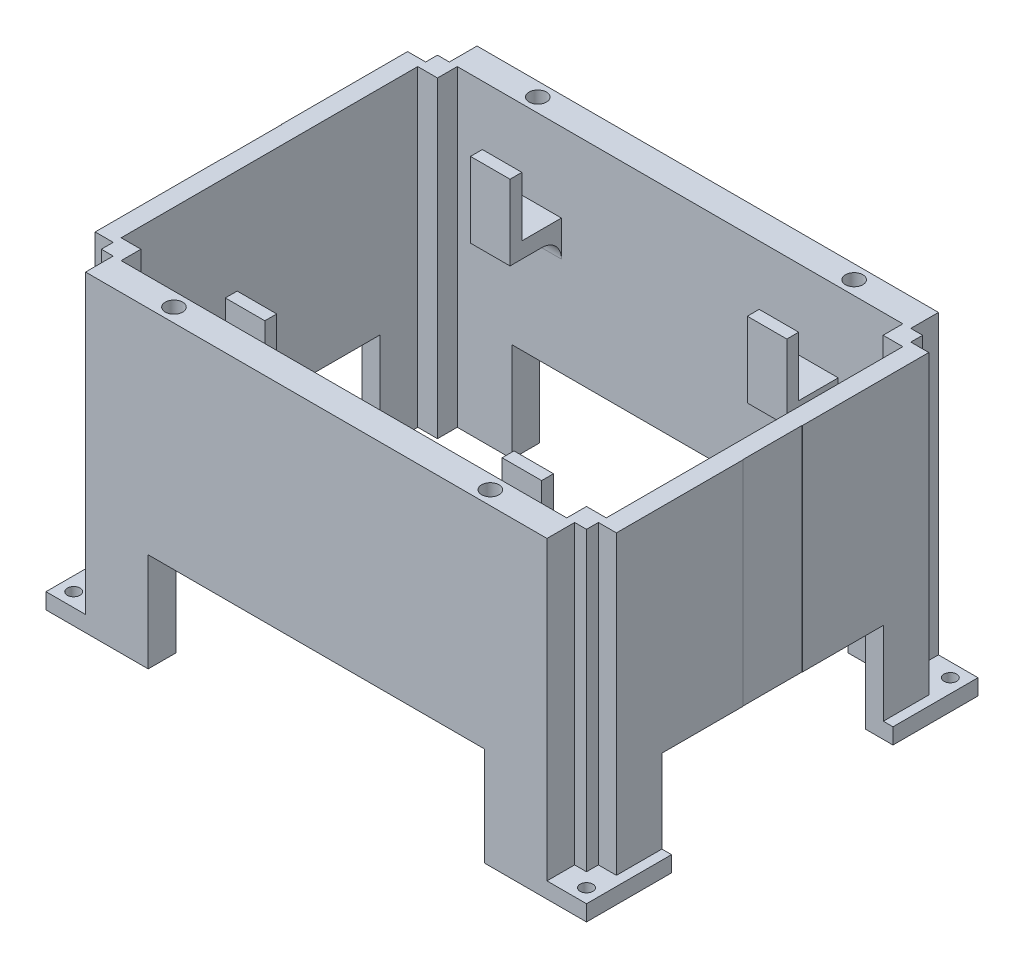
SolidWorks part; units mm, degrees
ref_plane "Front Plane" through (0, 0, 0) normal (0, 0, 1) x (1, 0, 0)
ref_plane "Top Plane" through (0, 0, 0) normal (0, 1, 0) x (1, 0, 0)
ref_plane "Right Plane" through (0, 0, 0) normal (1, 0, 0) x (0, 0, -1)
sketch "Sketch1" plane through (0, 0, 0) normal (0, 1, 0) x (1, 0, 0)
  line L0 (-68.342, -49.5) -> (-68.342, 49.5)
  line L1 (-61.342, -42.5) -> (61.342, -42.5)
  line L2 (-61.342, -42.5) -> (-61.342, 42.5)
  line L3 (-61.342, 42.5) -> (61.342, 42.5)
  line L4 (61.342, -42.5) -> (61.342, 42.5)
  line L5 (-61.342, -42.5) -> (61.342, 42.5) construction
  line L6 (-61.342, 42.5) -> (61.342, -42.5) construction
  line L7 (-68.342, 49.5) -> (68.342, 49.5)
  line L8 (68.342, -49.5) -> (68.342, 49.5)
  line L9 (-68.342, -49.5) -> (68.342, -49.5)
  line L10 (-68.342, 0) -> (-65.842, 0) construction
  line L11 (-65.842, 0) -> (-65.842, 7.5) construction
  line L12 (0, 0) -> (0, 42.5) construction
  line L13 (-70.842, -7.5) -> (-65.842, -7.5)
  line L14 (-70.842, -7.5) -> (-70.842, 7.5)
  line L15 (-70.842, 7.5) -> (-65.842, 7.5)
  line L16 (-65.842, -7.5) -> (-65.842, 7.5)
  line L17 (-70.842, -7.5) -> (-65.842, 7.5) construction
  line L18 (-70.842, 7.5) -> (-65.842, -7.5) construction
  line L19 (-72.842, -9.5) -> (-72.842, 9.5)
  line L20 (-72.842, 9.5) -> (-63.842, 9.5)
  line L21 (-63.842, -9.5) -> (-63.842, 9.5)
  line L22 (-72.842, -9.5) -> (-63.842, -9.5)
  line L23 (72.842, -9.5) -> (63.842, -9.5)
  line L24 (63.842, -9.5) -> (63.842, 9.5)
  line L25 (72.842, 9.5) -> (63.842, 9.5)
  line L26 (72.842, -9.5) -> (72.842, 9.5)
  line L27 (70.842, 7.5) -> (65.842, 7.5)
  line L28 (65.842, -7.5) -> (65.842, 7.5)
  line L29 (70.842, -7.5) -> (65.842, -7.5)
  line L30 (70.842, -7.5) -> (70.842, 7.5)
  line L31 (61.342, -37.5) -> (56.342, -37.5)
  line L32 (-61.342, -42.5) -> (-56.342, -42.5)
  line L33 (-61.342, -42.5) -> (-61.342, -37.5)
  line L34 (-61.342, -37.5) -> (-56.342, -37.5)
  line L35 (-56.342, -42.5) -> (-56.342, -37.5)
  line L36 (-61.342, 42.5) -> (-56.342, 42.5)
  line L37 (-61.342, 42.5) -> (-61.342, 37.5)
  line L38 (-61.342, 37.5) -> (-56.342, 37.5)
  line L39 (-56.342, 42.5) -> (-56.342, 37.5)
  line L40 (56.342, -42.5) -> (56.342, -37.5)
  line L41 (61.342, -42.5) -> (56.342, -42.5)
  line L42 (61.342, -42.5) -> (61.342, -37.5)
  line L43 (61.342, 37.5) -> (56.342, 37.5)
  line L44 (56.342, 42.5) -> (56.342, 37.5)
  line L45 (61.342, 42.5) -> (56.342, 42.5)
  line L46 (61.342, 42.5) -> (61.342, 37.5)
  point P0 (0, 0)
  dimension "D2" = 2
  dimension "D1" = 7
extrude "Boss-Extrude1" add sketch "Sketch1" along normal blind 4 contours L25 L8 L7 L0 L20 L21 L22 L9 L23 L24 L4 L1 L2 L3 | L0 L22 L21 L20 L15 L16 L13 | L8 L29 L28 L27 L25 L24 L23 region at (-66.6543, 0, 29.5) region at (-65.3108, 0, 0) region at (65.3108, 0, 0)
sketch "Sketch3" plane through (0, 0, 0) normal (0, 1, 0) x (1, 0, 0)
  line L0 (0, 0) -> (13.5974, 0) construction
  line L1 (0, 0) -> (0, -8.9797) construction
  line L2 (64.8156, -49.5) -> (64.8156, -46) construction
  line L3 (-68.342, -49.5) -> (68.342, -49.5) construction
  line L4 (68.342, -46) -> (64.842, -46) construction
  line L5 (68.342, -49.5) -> (68.342, -7.5) construction
  line L6 (0, 0) -> (0, 37.5) construction
  line L7 (0, 37.5) -> (-37.5, 37.5) construction
  circle A0 centre (64.842, -46) radius 1.6
  circle A1 centre (64.842, 46) radius 1.6
  circle A2 centre (-64.842, 46) radius 1.6
  circle A3 centre (-64.842, -46) radius 1.6
  circle A4 centre (-37.5, 37.5) radius 2.2
  circle A5 centre (37.5, 37.5) radius 2.2
  circle A6 centre (37.5, -37.5) radius 2.2
  circle A7 centre (-37.5, -37.5) radius 2.2
extrude "Cut-Extrude3" cut sketch "Sketch3" along normal up to next contours A2 | A3 | A0 | A1 region at (64.842, 0, 46) region at (64.842, 0, -46) region at (-64.842, 0, -46) region at (-64.842, 0, 46)
sketch "Sketch4" plane through (0, 4, 0) normal (0, 1, 0) x (1, 0, 0)
  line L0 (-61.342, 42.5) -> (-58.342, 42.5) construction
  line L1 (-61.342, 42.5) -> (61.342, 42.5) construction
  line L2 (-61.342, 42.5) -> (-61.342, 39.5) construction
  line L3 (-61.342, -42.5) -> (-61.342, 42.5) construction
  line L4 (-61.342, -42.5) -> (-61.342, -39.5) construction
  line L5 (61.342, 42.5) -> (58.342, 42.5) construction
  line L6 (-68.342, 49.5) -> (68.342, 49.5) construction
  line L7 (-58.342, 42.5) -> (58.342, 42.5)
  line L8 (-58.342, 42.5) -> (-58.342, 49.5)
  line L9 (-58.342, 49.5) -> (58.342, 49.5)
  line L10 (58.342, 42.5) -> (58.342, 49.5)
  line L11 (-55, 0) -> (55, 0) construction
  line L12 (-61.342, -39.5) -> (-65.9042, -39.5)
  line L13 (-61.342, -39.5) -> (-61.342, 39.5)
  line L14 (-61.342, 39.5) -> (-65.9042, 39.5)
  line L15 (-65.9042, -39.5) -> (-65.9042, 39.5)
  line L16 (-58.342, -49.5) -> (58.342, -49.5)
  line L17 (58.342, -42.5) -> (58.342, -49.5)
  line L18 (-58.342, -42.5) -> (58.342, -42.5)
  line L19 (-58.342, -42.5) -> (-58.342, -49.5)
  line L20 (0, -55) -> (0, 55) construction
  line L21 (61.342, 39.5) -> (65.9042, 39.5)
  line L22 (65.9042, -39.5) -> (65.9042, 39.5)
  line L23 (61.342, -39.5) -> (65.9042, -39.5)
  line L24 (61.342, -39.5) -> (61.342, 39.5)
  line M12 (-68.342, 7.5) -> (-65.842, 7.5)
  line M13 (-65.842, 7.5) -> (-65.842, -7.5)
  line M14 (-65.842, -7.5) -> (-68.342, -7.5)
  line M16 (-68.342, -49.5) -> (68.342, -49.5)
  line M18 (68.342, -7.5) -> (65.842, -7.5)
  line M19 (65.842, -7.5) -> (65.842, 7.5)
  line M20 (65.842, 7.5) -> (68.342, 7.5)
  line M22 (68.342, 49.5) -> (-68.342, 49.5)
  line M23 (61.342, 42.5) -> (61.342, -42.5)
  line M24 (61.342, -42.5) -> (-61.342, -42.5)
  line M25 (-61.342, -42.5) -> (-61.342, 42.5)
  line M26 (-61.342, 42.5) -> (61.342, 42.5)
extrude "Boss-Extrude2" add sketch "Sketch4" along normal blind 75 contours L15 L12 L14 M25 M12 M13 M14 | L10 L8 M26 M22 | L19 L17 M24 M16 | L23 L22 L21 M23 M18 M19 M20 region at (0, 4, -46) region at (-63.6173, 4, 0) region at (63.6173, 4, 0) region at (0, 4, 46)
extrude "Boss-Extrude3" add sketch "Sketch1<3>" along normal blind 79 contours L39 L3 L2 L38 | L1 L35 L34 L2 | L40 L1 L4 L31 | L3 L44 L43 L4 region at (-58.842, 0, 40) region at (58.842, 0, 40) region at (-58.842, 0, -40) region at (58.842, 0, -40)
sketch "Sketch1<3>" plane through (0, 0, 0) normal (0, 1, 0) x (1, 0, 0) same geometry as "Sketch1"
sketch "Sketch5" plane through (0, 0, 49.5) normal (0, 0, 1) x (1, 0, 0)
  line L0 (-42.5, 0) -> (42.5, 0)
  line L1 (-68.342, 0) -> (68.342, 0) construction
  line L2 (-42.5, 0) -> (-42.5, 25) construction
  line L4 (-42.5, 25) -> (42.5, 25)
  line L5 (-42.5, 25) -> (-42.5, 0)
  line L6 (-42.5, 0) -> (42.5, 0)
  line L7 (42.5, 25) -> (42.5, 0)
  point P6 (0, 0)
  line M2 (-68.342, 0) -> (68.342, 0)
extrude "Cut-Extrude4" cut sketch "Sketch5" against normal through all contours L7 L4 L5 M2 region at (0, 12.5, 49.5)
sketch "Sketch6" plane through (68.342, 0, 0) normal (1, 0, 0) x (0, 0, -1)
  line L0 (-28, 0) -> (28, 0)
  line L1 (7.5, 0) -> (49.5, 0) construction
  line L2 (-28, 0) -> (-28, 25) construction
  line L4 (-28, 25) -> (28, 25)
  line L5 (-28, 25) -> (-28, 0)
  line L6 (-28, 0) -> (28, 0)
  line L7 (28, 25) -> (28, 0)
  point P6 (0, 0)
  line M3 (49.5, 4) -> (7.5, 4)
  line M4 (7.5, 4) -> (7.5, 0)
extrude "Cut-Extrude5" cut sketch "Sketch6" against normal through all and the other way through all contours L7 L4 L5 L0 M4 M3 | L5 L4 L7 L6 region at (68.342, 13.1533, 1.1043)
sketch "Sketch7" plane through (0, 79, 0) normal (0, 1, 0) x (1, 0, 0)
  line L0 (-39.4781, 42.5) -> (40.5219, 42.5)
  line L1 (-56.342, 42.5) -> (56.342, 42.5) construction
  line L2 (40.5219, 42.5) -> (40.5219, 46)
  line L3 (-43.45, 0) -> (43.45, 0) construction
  line L4 (-39.4781, 46) -> (-39.4781, -46)
  circle A0 centre (40.5219, 46) radius 2.2
  circle A1 centre (-39.4781, 46) radius 2.2
  circle A2 centre (40.5219, -46) radius 2.2
  circle A3 centre (-39.4781, -46) radius 2.2
  point P5 (0.5219, 42.5)
extrude "Cut-Extrude6" cut sketch "Sketch7" against normal blind 10 contours A0 | A2 | A3 | A1 region at (39.0102, 79, -47.5116) region at (-40.9898, 79, -47.5116) region at (-37.9665, 79, 44.4884) region at (40.5219, 79, 46)
sketch "Sketch8" plane through (0, 0, -42.5) normal (0, 0, 1) x (1, 0, 0)
  line L0 (0, 79) -> (-35, 79)
  line L1 (-58.342, 79) -> (58.342, 79) construction
  line L2 (-35, 79) -> (-35, 59)
  line L3 (-40, 59) -> (-30, 59)
  line L4 (-40, 59) -> (-40, 55)
  line L6 (-40, 55) -> (-30, 55)
  line L7 (-40, 55) -> (-40, 59)
  line L8 (-40, 59) -> (-30, 59)
  line L9 (-30, 55) -> (-30, 59)
  point P8 (-35, 59)
extrude "Boss-Extrude4" add sketch "Sketch8" along normal blind 13 contours L6 L9 L3 L4 region at (-35, 57, -42.5)
sketch "Sketch9" plane through (0, 59, 0) normal (0, 1, 0) x (1, 0, 0)
  line L0 (-40, 29.5) -> (-40, 32.5) construction
  line L1 (-40, 29.5) -> (-40, 42.5) construction
  line L2 (-30, 29.5) -> (-30, 42.5) construction
  line L3 (-40, 32.5) -> (-30, 32.5)
  line L4 (-40, 32.5) -> (-40, 29.5)
  line L5 (-40, 29.5) -> (-30, 29.5)
  line L6 (-30, 32.5) -> (-30, 29.5)
extrude "Boss-Extrude5" add sketch "Sketch9" along normal blind 15
fillet "Fillet1" radius 5 1 edges at (-35, 55, -42.5)
mirror "Mirror1" about plane through (0, 0, 0) normal (0, 0, 1) of "Boss-Extrude5", "Boss-Extrude4"
mirror "Mirror2" about plane through (0, 0, 0) normal (1, 0, 0) of "Mirror1", "Boss-Extrude5", "Boss-Extrude4"
